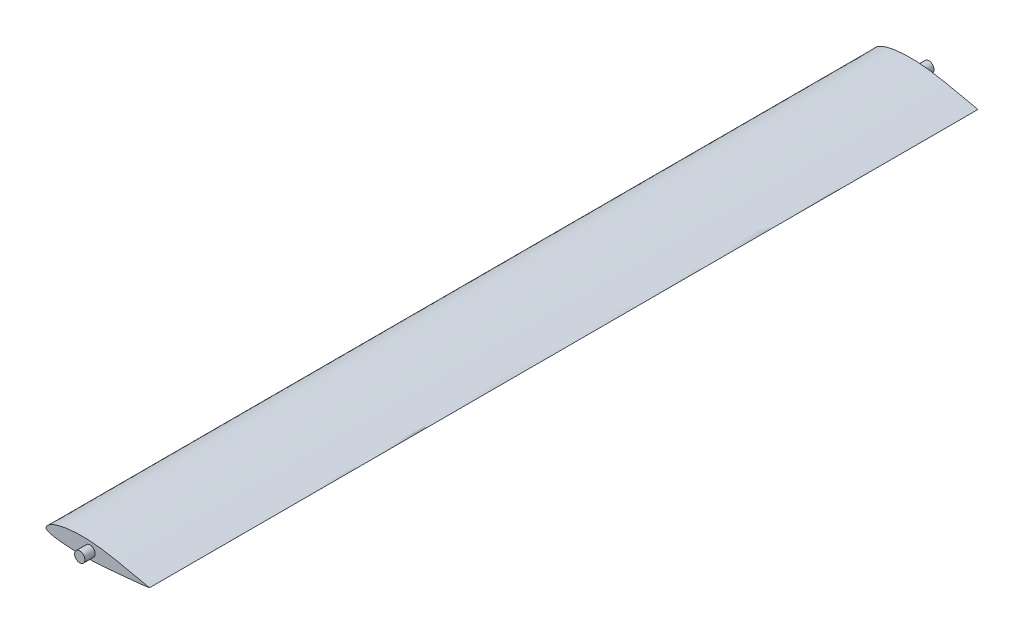
SolidWorks part; units mm, degrees
ref_plane "Front Plane" through (0, 0, 0) normal (0, 0, 1) x (1, 0, 0)
ref_plane "Top Plane" through (0, 0, 0) normal (0, 1, 0) x (1, 0, 0)
ref_plane "Right Plane" through (0, 0, 0) normal (1, 0, 0) x (0, 0, -1)
other "Center of Mass"
curve "Curve1"
  spline degree 3 poles (2527.2785, -0.7303, 0) (2543.335, -0.1392, 0) (2527.3878, 1.7851, 0) (2515.5292, 5.8817, 0) (2488.2293, 12.9019, 0) (2456.0322, 21.5149, 0) (2414.6563, 30.5876, 0) (2365.9234, 40.6704, 0) (2309.555, 52.1365, 0) (2246.3285, 65.0018, 0) (2176.8454, 79.2335, 0) (2101.848, 94.6989, 0) (2022.0633, 111.2691, 0) (1938.2558, 128.7364, 0) (1851.199, 146.8068, 0) (1761.6772, 165.1783, 0) (1670.4955, 183.4458, 0) (1578.3561, 201.2005, 0) (1485.682, 217.4895, 0) (1392.8204, 231.8087, 0) (1300.1686, 244.3615, 0) (1207.9719, 254.5594, 0) (1116.615, 262.183, 0) (1026.4456, 267.4992, 0) (937.7782, 270.0921, 0) (850.9529, 270.2351, 0) (766.3332, 267.999, 0) (684.3606, 263.32, 0) (605.4281, 256.5267, 0) (529.9495, 247.6046, 0) (458.3473, 236.734, 0) (390.9977, 223.9986, 0) (328.257, 209.4348, 0) (270.4064, 193.2972, 0) (217.6983, 175.6631, 0) (170.4327, 156.5598, 0) (128.6047, 136.5626, 0) (92.5134, 115.5502, 0) (62.2563, 94.0194, 0) (37.7679, 72.3218, 0) (19.4549, 50.4341, 0) (6.8635, 29.1069, 0) (0.0718, 9.6345, 0) (-1.2744, -9.2497, 0) (10.506, -25.1906, 0) (29.9207, -37.7525, 0) (56.6108, -50.6963, 0) (90.7122, -62.9707, 0) (132.0134, -74.4238, 0) (180.2672, -85.0557, 0) (235.1786, -94.9227, 0) (296.4203, -103.7415, 0) (363.5588, -111.7313, 0) (436.1664, -118.7122, 0) (513.7173, -124.7171, 0) (595.729, -129.6182, 0) (681.6869, -133.281, 0) (771.0708, -135.7351, 0) (863.36, -136.8526, 0) (958.0353, -136.4946, 0) (1054.5924, -134.8917, 0) (1152.5523, -131.7102, 0) (1251.3817, -127.126, 0) (1350.6396, -121.2679, 0) (1449.8899, -113.972, 0) (1548.7058, -105.6527, 0) (1646.5442, -96.8886, 0) (1742.6645, -87.746, 0) (1836.3702, -78.5986, 0) (1926.9226, -69.5519, 0) (2013.6035, -60.8665, 0) (2095.6864, -52.6026, 0) (2172.4693, -44.8786, 0) (2243.2725, -37.7621, 0) (2307.4392, -31.3213, 0) (2364.4156, -25.3996, 0) (2413.512, -19.9897, 0) (2455.1291, -14.6994, 0) (2487.6157, -8.8211, 0) (2515.1953, -4.0042, 0) (2527.2785, -0.7303, 0) (2543.335, -0.1392, 0) (2527.3878, 1.7851, 0) knots -0.00957 -0.004539 -0.001196 0 0.001194 0.00454 0.009601 0.016135 0.024161 0.033728 0.044763 0.057157 0.070769 0.085471 0.10111 0.11754 0.134608 0.152144 0.169995 0.187984 0.206002 0.224 0.241912 0.259664 0.277235 0.294525 0.311503 0.328142 0.344355 0.360082 0.375262 0.389821 0.403699 0.416824 0.429154 0.440657 0.451284 0.461038 0.469901 0.477873 0.484977 0.491187 0.496596 0.501303 0.50529 0.508453 0.511643 0.51604 0.521704 0.528625 0.536817 0.546289 0.556976 0.568832 0.581797 0.595781 0.610696 0.626441 0.642935 0.660077 0.677763 0.695909 0.714417 0.73319 0.752163 0.771203 0.790259 0.809283 0.828121 0.846641 0.864703 0.882162 0.898875 0.914705 0.929514 0.94317 0.955547 0.966536 0.976028 0.983961 0.99043 0.995461 0.998804 1 1.001194 1.00454 1.009601 periodic
sketch "Sketch1" plane through (0, 0, 0) normal (0, 0, 1) x (1, 0, 0)
  line L0 (0, 0) -> (0, 7.9474) construction
  line L1 (0, 0) -> (50, 0) construction
  spline S1 degree 3 poles (49.7496, -0.0143) (50.0656, -0.0028) (49.7518, 0.0352) (49.5184, 0.116) (48.9811, 0.2544) (48.3475, 0.4242) (47.5332, 0.6031) (46.5741, 0.8019) (45.4647, 1.0281) (44.2204, 1.2818) (42.8529, 1.5625) (41.3769, 1.8675) (39.8067, 2.1943) (38.1573, 2.5388) (36.4439, 2.8951) (34.6821, 3.2575) (32.8876, 3.6178) (31.0742, 3.968) (29.2503, 4.2893) (27.4226, 4.5719) (25.5991, 4.8198) (23.7846, 5.0212) (21.9865, 5.172) (20.2118, 5.2774) (18.4666, 5.3292) (16.7577, 5.3327) (15.0921, 5.2894) (13.4787, 5.198) (11.9251, 5.0649) (10.4394, 4.8899) (9.03, 4.6765) (7.7043, 4.4264) (6.4693, 4.1403) (5.3305, 3.8231) (4.2929, 3.4765) (3.3625, 3.1009) (2.539, 2.7076) (1.8285, 2.2943) (1.2328, 1.8708) (0.7506, 1.4439) (0.39, 1.0133) (0.142, 0.5936) (0.0082, 0.2104) (-0.0185, -0.1613) (0.2132, -0.4751) (0.5953, -0.7225) (1.1205, -0.9775) (1.7916, -1.2194) (2.6044, -1.4451) (3.5541, -1.6548) (4.6348, -1.8495) (5.8401, -2.0235) (7.1615, -2.1813) (8.5905, -2.3193) (10.1168, -2.4382) (11.731, -2.5353) (13.4228, -2.6081) (15.1821, -2.6571) (16.9986, -2.6799) (18.862, -2.6736) (20.7625, -2.6428) (22.6906, -2.581) (24.6358, -2.4916) (26.5895, -2.3771) (28.5431, -2.2343) (30.4881, -2.0714) (32.4138, -1.8997) (34.3058, -1.7205) (36.1502, -1.5413) (37.9326, -1.3639) (39.6387, -1.1937) (41.2544, -1.0317) (42.7657, -0.8803) (44.1594, -0.7408) (45.4224, -0.6146) (46.5439, -0.4985) (47.5102, -0.3924) (48.3294, -0.2886) (48.9689, -0.1732) (49.5118, -0.0786) (49.7496, -0.0143) (50.0656, -0.0028) (49.7518, 0.0352) knots -0.00957 -0.004539 -0.001196 0 0.001194 0.00454 0.009601 0.016135 0.024161 0.033728 0.044763 0.057157 0.070769 0.085471 0.10111 0.11754 0.134608 0.152144 0.169995 0.187984 0.206002 0.224 0.241912 0.259664 0.277235 0.294525 0.311503 0.328142 0.344355 0.360082 0.375262 0.389821 0.403699 0.416824 0.429154 0.440657 0.451284 0.461038 0.469901 0.477873 0.484977 0.491187 0.496596 0.501303 0.50529 0.508453 0.511643 0.51604 0.521704 0.528625 0.536817 0.546289 0.556976 0.568832 0.581797 0.595781 0.610696 0.626441 0.642935 0.660077 0.677763 0.695909 0.714417 0.73319 0.752163 0.771203 0.790259 0.809283 0.828121 0.846641 0.864703 0.882162 0.898875 0.914705 0.929514 0.94317 0.955547 0.966536 0.976028 0.983961 0.99043 0.995461 0.998804 1 1.001194 1.00454 1.009601 only from (50, 0) to (50, 0)
  dimension "D1" = 50
extrude "Boss-Extrude1" add sketch "Sketch1" along normal mid plane 400 contours S1
other "Center of Mass Reference Point1"
sketch "Sketch3" plane through (0, 0, 0) normal (0, 0, 1) x (1, 0, 0)
  circle A0 centre (21.2826, 1.0439) radius 2.5
  point P2 (0, 0)
  point P3 (49.5707, -18.1893)
  point P4 (40.5044, 0.8133)
  dimension "D1" = 5
  dimension "D2" = 0
  dimension "D3" = 0
extrude "Boss-Extrude2" add sketch "Sketch3" along normal blind 5 from surface
mirror "Mirror1" about plane through (0, 0, 0) normal (0, 0, 1) of "Boss-Extrude2"
